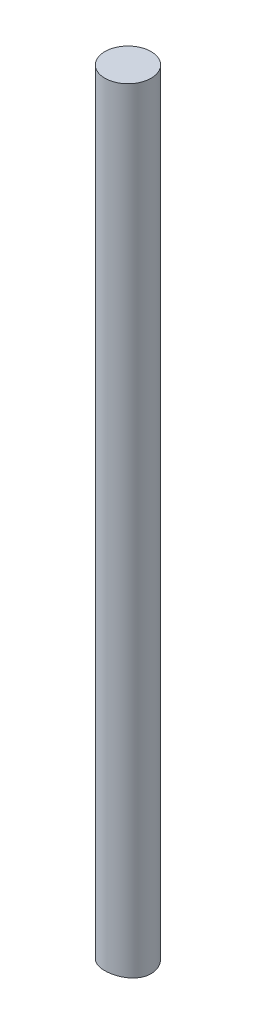
SolidWorks part; units mm, degrees
ref_plane "Front Plane" through (0, 0, 0) normal (0, 0, 1) x (1, 0, 0)
ref_plane "Top Plane" through (0, 0, 0) normal (0, 1, 0) x (1, 0, 0)
ref_plane "Right Plane" through (0, 0, 0) normal (1, 0, 0) x (0, 0, -1)
sketch "Sketch1" plane through (0, 0, 0) normal (0, 0, 1) x (1, 0, 0)
  line L0 (0, -150.95) -> (0, 150.95)
  point P4 (0, 0)
  dimension "D1" = 301.9
sketch "Sketch2" plane through (0, 0, 0) normal (0, 1, 0) x (1, 0, 0)
  circle A0 centre (0, 0) radius 9
  dimension "D1" = 18
sweep "Sweep1" add profiles "Sketch2" path "Sketch1"
sketch "Sketch3" plane through (0, 0, 0) normal (0, 0, 1) x (1, 0, 0)
  line L0 (-9, -150.95) -> (9, -150.95)
  line L1 (0, -150.95) -> (0, -230.95)
  circle A0 centre (0, -190.4438) radius 40.5063
  dimension "D1" = 80
extrude "Cut-Extrude1" cut sketch "Sketch3" against normal through all both and the other way through all contours L0 A0 region at (0, -150.5446, 0)
ref_axis "Axis1" through (0, 150.95, 0) along (0, -1, 0)
